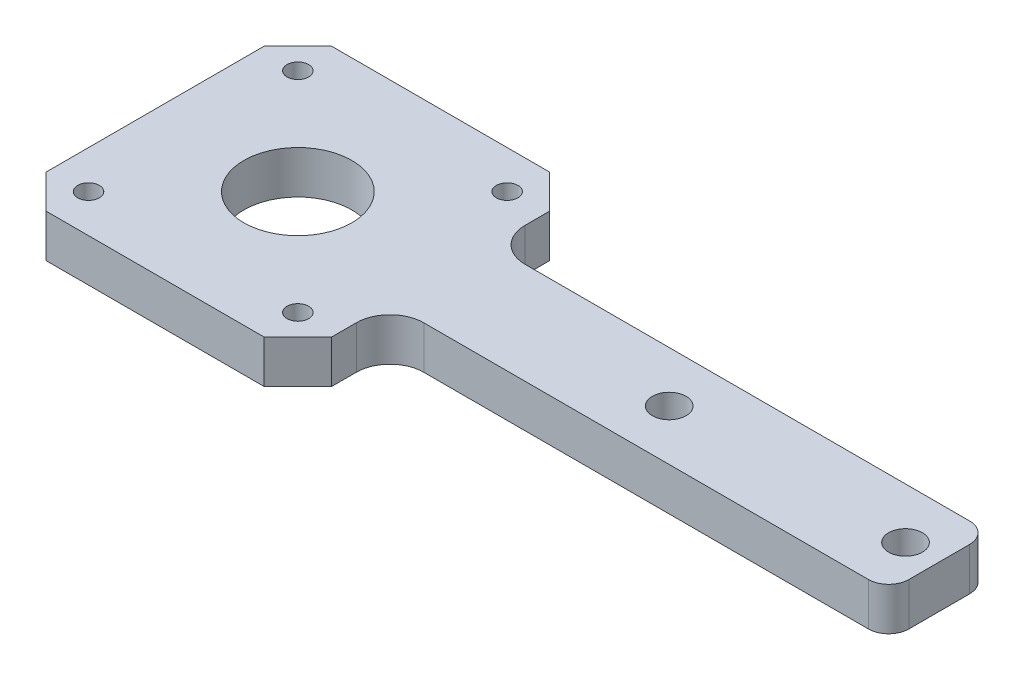
SolidWorks part; units mm, degrees
material "AISI 4130 Steel, annealed at 865C"
ref_plane "Front Plane" through (0, 0, 0) normal (0, 0, 1) x (1, 0, 0)
ref_plane "Top Plane" through (0, 0, 0) normal (0, 1, 0) x (1, 0, 0)
ref_plane "Right Plane" through (0, 0, 0) normal (1, 0, 0) x (0, 0, -1)
sketch "Sketch1" plane through (0, 0, 0) normal (0, 1, 0) x (1, 0, 0)
  line L0 (0, 0) -> (95, 0) construction
  line L1 (-15.5, 15.5) -> (15.5, 15.5) construction
  line L2 (-15.5, 15.5) -> (-15.5, -15.5) construction
  line L3 (-15.5, -15.5) -> (15.5, -15.5) construction
  line L4 (15.5, 15.5) -> (15.5, -15.5) construction
  line L5 (-15.5, 15.5) -> (15.5, -15.5) construction
  line L6 (-15.5, -15.5) -> (15.5, 15.5) construction
  line L7 (-21.15, 21.15) -> (21.15, 21.15)
  line L8 (-21.15, 21.15) -> (-21.15, -21.15)
  line L9 (-21.15, -21.15) -> (21.15, -21.15)
  line L11 (-21.15, 21.15) -> (21.15, -21.15) construction
  line L12 (-21.15, -21.15) -> (21.15, 21.15) construction
  line L13 (21.15, 7.5) -> (95, 7.5)
  line L14 (95, 7.5) -> (95, -7.5)
  line L15 (95, -7.5) -> (21.15, -7.5)
  line L16 (21.15, 21.15) -> (21.15, 7.5)
  line L17 (21.15, 7.5) -> (21.15, -7.5) construction
  line L18 (21.15, -7.5) -> (21.15, -21.15)
  circle A0 centre (-15.5, 15.5) radius 1.6
  circle A1 centre (15.5, 15.5) radius 1.6
  circle A2 centre (15.5, -15.5) radius 1.6
  circle A3 centre (-15.5, -15.5) radius 1.6
  circle A4 centre (0, 0) radius 8
  circle A5 centre (90, 0) radius 2.5
  circle A6 centre (55, 0) radius 2.5
  point P0 (0, 0)
  point P10 (0, 0)
  dimension "D2" = 3.2
  dimension "D4" = 16
  dimension "D9" = 5
  dimension "D1" = 31
  dimension "D3" = 42.3
  dimension "D5" = 15
  dimension "D6" = 95
  dimension "D7" = 5
  dimension "D8" = 35
  dimension "D10" = 55
extrude "Boss-Extrude2" add sketch "Sketch1" along normal blind 6.35
chamfer "Chamfer2" distance 5 angle 45 4 edges at (-21.15, 3.175, -21.15) (21.15, 3.175, -21.15) (21.15, 3.175, 21.15) (-21.15, 3.175, 21.15)
fillet "Fillet1" radius 3 2 edges at (95, 3.175, -7.5) (95, 3.175, 7.5)
fillet "Fillet2" radius 5 2 edges at (21.15, 3.175, -7.5) (21.15, 3.175, 7.5)
